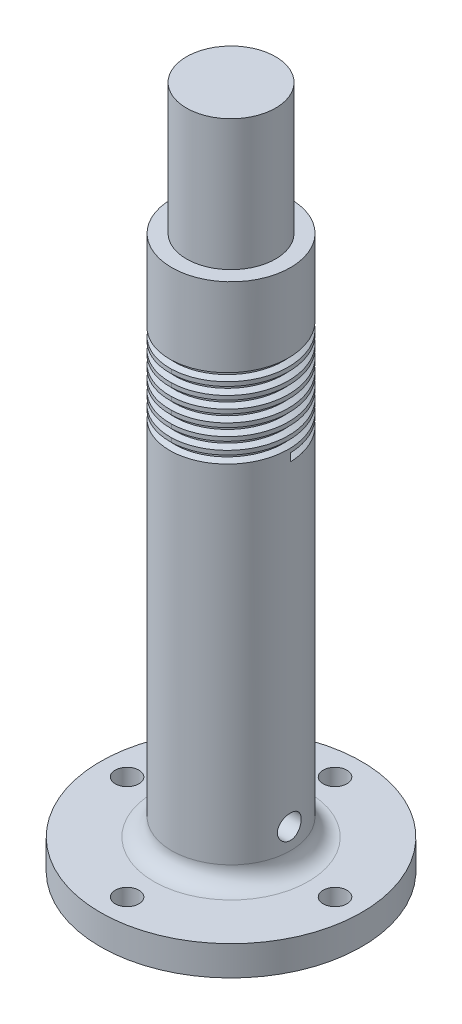
SolidWorks part; units mm, degrees
ref_plane "Front Plane" through (0, 0, 0) normal (0, 0, 1) x (1, 0, 0)
ref_plane "Top Plane" through (0, 0, 0) normal (0, 1, 0) x (1, 0, 0)
ref_plane "Right Plane" through (0, 0, 0) normal (1, 0, 0) x (0, 0, -1)
sketch "Sketch1" plane through (0, 0, 0) normal (0, 1, 0) x (1, 0, 0)
  circle A0 centre (0, 0) radius 22
  circle A1 centre (0, 0) radius 17.5 construction
  circle A2 centre (0, 17.5) radius 2
  circle A3 centre (17.5, 0) radius 2
  circle A4 centre (0, -17.5) radius 2
  circle A5 centre (-17.5, 0) radius 2
  point P15 (0, 0)
  dimension "D1" = 44
  dimension "D2" = 35
  dimension "D3" = 4
  dimension "D4" = 4
extrude "Boss-Extrude1" add sketch "Sketch1" along normal blind 5
sketch "Sketch2" plane through (0, 5, 0) normal (0, 1, 0) x (1, 0, 0)
  circle A0 centre (0, 0) radius 10
  dimension "D1" = 20
extrude "Boss-Extrude2" add sketch "Sketch2" along normal blind 160
fillet "Fillet1" radius 3 1 edges at (0, 5, 10)
sketch "Sketch3" plane through (0, 0, 0) normal (1, 0, 0) x (0, 0, -1)
  line L0 (-10, 8) -> (10, 8) construction
  circle A0 centre (0, 11.5) radius 2
  dimension "D1" = 4
  dimension "D2" = 3.5
extrude "Cut-Extrude1" cut sketch "Sketch3" against normal mid plane 100
ref_plane "Plane3" through (0, 105, 0) normal (0, 1, 0) x (1, 0, 0)
sketch "Sketch7" plane through (0, 105, 0) normal (0, 1, 0) x (1, 0, 0)
  circle A0 centre (0, 0) radius 7.5
  circle A1 centre (0, 0) radius 10
  dimension "D1" = 15
  dimension "D2" = 20
extrude "Cut-Extrude2" cut sketch "Sketch7" along normal blind 100 and the other way blind 12
thread "Thread1" pitch 1.5 method cut profile "Thread Profile2" start angle 0, offset 12, length 15, pitch 2, diameter 20
ref_plane "Plane4" through (-10, 81, 0) normal (0, 0, 1) x (-1, 0, 0)
sketch "Thread Profile2" plane through (-10, 81, 0) normal (0, 0, 1) x (-1, 0, 0)
  line L0 (0, 0) -> (0, 1.5) construction
  line L11 (0, 0) -> (0, 1.3125)
  line L12 (0, 1.3125) -> (-0.8119, 0.8437)
  line L13 (-0.8119, 0.8437) -> (-0.8119, 0.4687)
  line L15 (-0.8119, 0.4687) -> (0, 0)
  line L17 (-0.8119, 0.6562) -> (0, 0.6562) construction
  point P2 (0, 0)
  dimension "Pitch" = 1.5
  dimension "Profile_Angle" = 60
  dimension "Profile_Land" = 0.375
  dimension "Profile_Height" = 0.8119
sketch "Sketch12" plane through (0, 165, 0) normal (0, 1, 0) x (1, 0, 0)
  circle A0 centre (0, 0) radius 7.5
  dimension "D1" = 15
extrude "Cut-Extrude4" cut sketch "Sketch12" against normal blind 50
